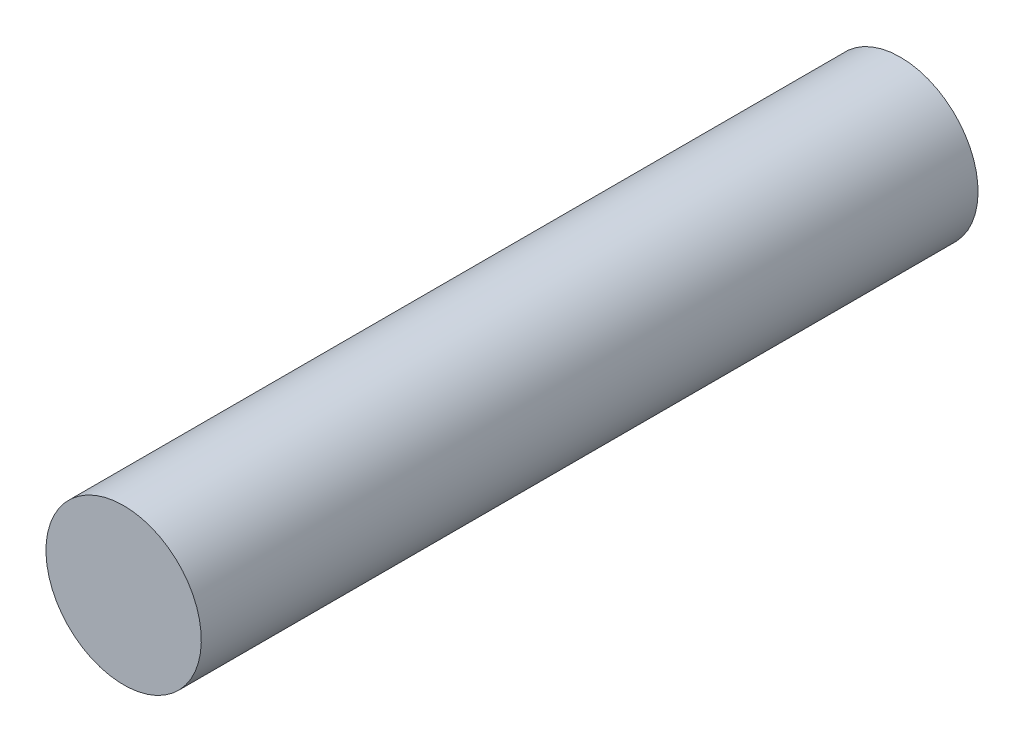
SolidWorks part; units mm, degrees
ref_plane "Front Plane" through (0, 0, 0) normal (0, 0, 1) x (1, 0, 0)
ref_plane "Top Plane" through (0, 0, 0) normal (0, 1, 0) x (1, 0, 0)
ref_plane "Right Plane" through (0, 0, 0) normal (1, 0, 0) x (0, 0, -1)
sketch "Sketch1" plane through (0, 0, 0) normal (1, 0, 0) x (0, 0, -1)
  line L0 (-15.875, 0) -> (15.875, 0) construction
  line L1 (3.4925, 0) -> (-3.4925, 0) construction
  line L2 (-11.9062, 3.175) -> (-11.9062, -3.175) construction
  line L3 (11.9062, 3.175) -> (11.9062, -3.175) construction
  line L4 (-15.875, 3.175) -> (-15.875, -3.175) construction
  line L5 (15.875, 3.175) -> (15.875, -3.175) construction
  line L6 (-15.875, 3.175) -> (-14.9679, 3.175) construction
  line L7 (0, 3.4925) -> (0, -3.4925) construction
  line L8 (-14.5143, 3.175) -> (-14.5143, -3.175) construction
  point P6 (0, 0)
  point P10 (-11.9062, 0)
  point P13 (11.9062, 0)
  point P16 (-15.875, 0)
  point P19 (15.875, 0)
  point P22 (-15.875, 3.175)
  point P25 (-14.5143, 0)
  dimension "Length" = 31.75
  dimension "Pitch" = 0.9071
  dimension "MajorDia" = 6.35
  dimension "D1" = 23.8125
  dimension "D2" = 11.9062
  dimension "D3" = 1.3607
sketch "Sketch2" plane through (0, 0, 0) normal (1, 0, 0) x (0, 0, -1)
  line L1 (-15.875, 3.175) -> (15.875, 3.175)
  line L2 (-15.875, 3.175) -> (-15.875, 0)
  line L3 (-15.875, 0) -> (15.875, 0)
  line L4 (15.875, 3.175) -> (15.875, 0)
  line L5 (0, 0) -> (0, 3.175) construction
  line L6 (-15.875, 1.5875) -> (15.875, 1.5875) construction
  point P612 (0, 1.5875)
revolve "Revolve1" add sketch "Sketch2" angle 360 about L0
chamfer "Chamfer1" distance 0.6804 angle 45 2 edges at (0, -3.175, -15.875) (0, -3.175, 15.875)
sketch "Sketch3" plane through (0, 0, 15.875) normal (0, 0, 1) x (1, 0, 0)
  circle A0 centre (0, 0) radius 3.175
  dimension "D1" = 6.35
curve "Helix/Spiral1" pitch 0.9071 height 32.6571 radius 3.175 centre (0, 0, 15.875) axis (0, 0, -1) start towards (0, 1, 0)
sketch "Sketch4" plane through (0, 0, 0) normal (1, 0, 0) x (0, 0, -1)
  line L0 (-16.7254, 3.2732) -> (-16.2719, 2.4876) construction
  line L1 (-16.2719, 2.4876) -> (-15.8183, 3.2732) construction
  line L2 (-16.7254, 3.2732) -> (-15.8183, 3.2732) construction
  line L3 (-16.3286, 2.5858) -> (-16.2152, 2.5858) construction
  line L4 (-16.2719, 2.5858) -> (-16.2719, 2.4876) construction
  line L5 (-16.6687, 3.175) -> (-15.875, 3.175) construction
  line L6 (-16.2719, 3.175) -> (-16.2719, 3.2732) construction
  line L7 (-16.6971, 3.2241) -> (-15.8467, 3.2241) construction
  line L8 (-16.2152, 2.5858) -> (-16.3286, 2.5858)
  line L9 (-16.3286, 2.5858) -> (-16.6971, 3.2241)
  line L10 (-16.6971, 3.2241) -> (-15.8467, 3.2241)
  line L11 (-15.8467, 3.2241) -> (-16.2152, 2.5858)
  point P13 (-16.2719, 3.2241)
  dimension "D1" = 60
  dimension "D2" = 0.9071
sweep "Cut-Sweep1" cut profiles "Sketch4" path "Helix/Spiral1"
sketch "Sketch5" plane through (0, 0, -15.875) normal (0, 0, -1) x (-1, 0, 0)
  circle A0 centre (0, 0) radius 3.175
  circle A1 centre (0, 0) radius 3.175 construction
extrude "Boss-Extrude1" add sketch "Sketch5" against normal up to surface (31.75 mm away) up to face at (0, 2.4946, 15.875)
equation "\"D1@Chamfer1\"=\"Pitch@Sketch1\"*.75"
equation "\"D1@Sketch3\"=\"MajorDia@Sketch1\""
equation "\"D3@Helix/Spiral1\"=\"Length@Sketch1\"+\"Pitch@Sketch1\""
equation "\"D4@Helix/Spiral1\"=\"Pitch@Sketch1\""
equation "\"D2@Sketch4\"=\"Pitch@Sketch1\""
equation "\"D3@Sketch4\"=\"D2@Sketch4\"/8"
equation "\"D1@Sketch1\"=\"Length@Sketch1\"*.75"
equation "\"D2@Sketch1\"=\"D1@Sketch1\"/2"
equation "\"D3@Sketch1\"=\"Pitch@Sketch1\"*1.5"
